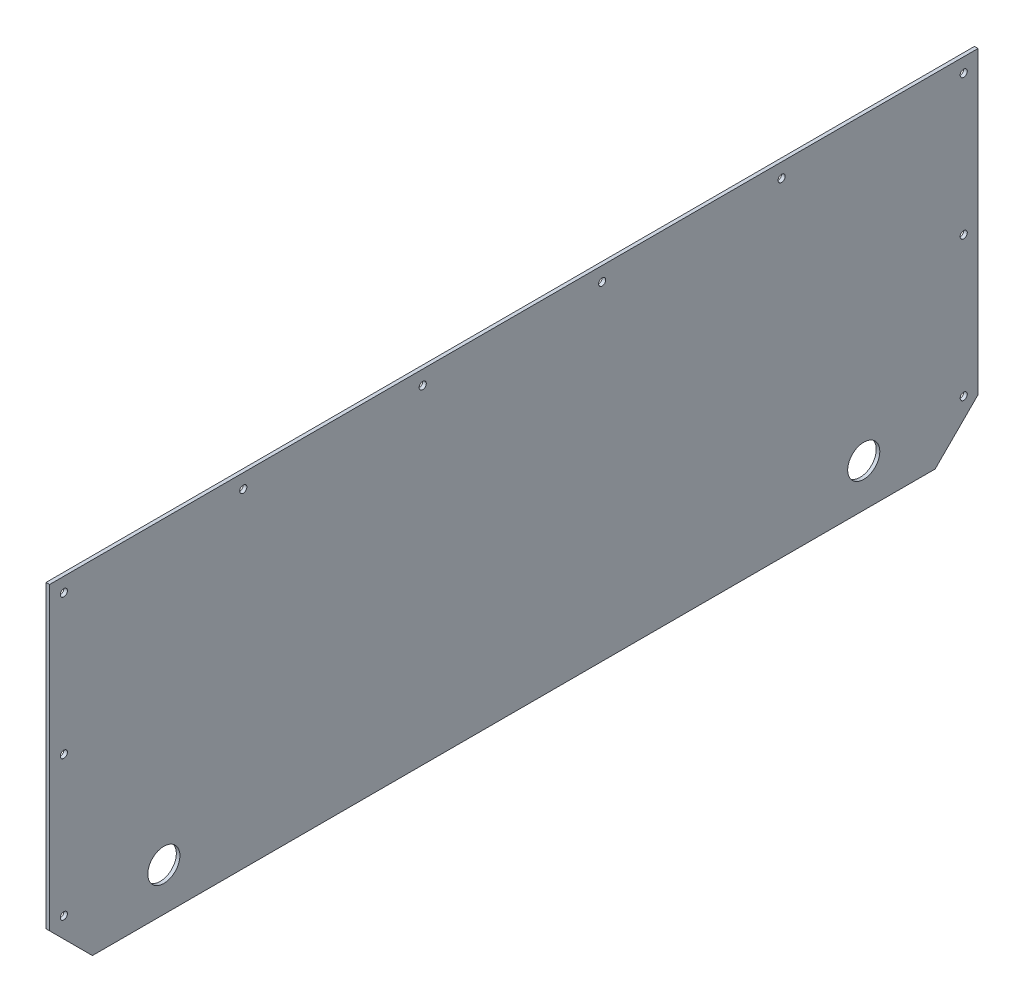
SolidWorks part; units mm, degrees
ref_plane "Front Plane" through (0, 0, 0) normal (0, 0, 1) x (1, 0, 0)
ref_plane "Top Plane" through (0, 0, 0) normal (0, 1, 0) x (1, 0, 0)
ref_plane "Right Plane" through (0, 0, 0) normal (1, 0, 0) x (0, 0, -1)
sketch "Sketch1" plane through (0, 0, 0) normal (0, 0, 1) x (1, 0, 0)
  line L0 (0, 0) -> (0, 304.8)
  dimension "D1" = 304.8
base flange "Base-Flange1" sketch "Sketch1" end condition mid plane depth 825.5 reverse direction no thickness 3.175 reverse thickness direction no bend radius 0.7366
sketch "Sketch6" plane through (3.175, 0, 0) normal (1, 0, 0) x (0, 0, -1)
  line L0 (-311.15, 38.1) -> (311.15, 38.1) construction
  line L1 (-412.75, 0) -> (-412.75, 304.8) construction
  line L2 (-412.75, 0) -> (412.75, 0) construction
  line L3 (-412.75, 38.1) -> (-374.65, 0)
  line L4 (-374.65, 0) -> (-412.75, 0)
  line L5 (-412.75, 0) -> (-412.75, 38.1)
  line L6 (0, 0) -> (0, 304.8) construction
  line L7 (-412.75, 304.8) -> (412.75, 304.8) construction
  line L8 (412.75, 0) -> (412.75, 38.1)
  line L9 (374.65, 0) -> (412.75, 0)
  line L10 (412.75, 38.1) -> (374.65, 0)
  line L11 (-400.05, 25.4) -> (-400.05, 304.8) construction
  line L12 (-412.75, 292.1) -> (412.75, 292.1) construction
  line L13 (412.75, 0) -> (412.75, 304.8) construction
  line L14 (400.05, 304.8) -> (400.05, 25.4) construction
  circle A0 centre (-311.15, 38.1) radius 76.2 construction
  circle A1 centre (311.15, 38.1) radius 76.2 construction
  circle A2 centre (-311.15, 38.1) radius 14.2875
  circle A3 centre (311.15, 38.1) radius 14.2875
  circle A4 centre (-400.05, 292.1) radius 3.175
  circle A5 centre (-400.05, 167.7303) radius 3.175
  circle A6 centre (-400.05, 43.3605) radius 3.175
  circle A7 centre (400.05, 43.3605) radius 3.175
  circle A8 centre (400.05, 292.1) radius 3.175
  circle A9 centre (400.05, 167.7303) radius 3.175
  circle A10 centre (-240.5062, 292.1) radius 3.175
  circle A11 centre (-80.9625, 292.1) radius 3.175
  circle A12 centre (78.5813, 292.1) radius 3.175
  circle A13 centre (238.125, 292.1) radius 3.175
  point P6 (0, 38.1)
  point P10 (-311.15, -38.1)
  dimension "D1" = 152.4
  dimension "D2" = 28.575
  dimension "D9" = 6.35
  dimension "D11" = 12.7
  dimension "D3" = 101.6
  dimension "D4" = 38.1
  dimension "D5" = 38.1
  dimension "D6" = 12.7
  dimension "D7" = 12.7
  dimension "D8" = 12.7
  dimension "D13" = 80.9625
  dimension "D10" = 3
  dimension "D12" = 5
extrude "Cut-Extrude1" cut sketch "Sketch6" against normal through all normal cut yes
sketch "Bend-Lines1" [suppressed] plane through (0, 0, 0) normal (0, 1, 0) x (1, 0, 0)
sketch "Bounding-Box1" [suppressed] plane through (0, 0, 0) normal (0, 1, 0) x (1, 0, 0)
sheet metal parameters "Sheet-Metal1" thickness 3.175 parameters "D1"=0.7366
flat pattern "Flat-Pattern1" [suppressed]
sketch "Bend-Lines2" plane through (0, 0, 0) normal (0, 1, 0) x (1, 0, 0)
sketch3d "Bounding-Box2" [suppressed]
  line L0 (-825.5, 0, 0) -> (0, 0, 0) construction
  line L1 (-825.5, 304.8, 0) -> (0, 304.8, 0) construction
  line L2 (-825.5, 0, 0) -> (-825.5, 304.8, 0) construction
  line L3 (0, 0, 0) -> (0, 304.8, 0) construction
sheet metal parameters "Sheet-Metal2" thickness 3.175 parameters "D1"=0.7366
flat pattern "Flat-Pattern1"
sketch "Bend-Lines2" plane through (0, 0, 0) normal (0, 1, 0) x (1, 0, 0)
sketch3d "Bounding-Box2" [suppressed]
  line L0 (-825.5, 0, 0) -> (0, 0, 0) construction
  line L1 (-825.5, 304.8, 0) -> (0, 304.8, 0) construction
  line L2 (-825.5, 0, 0) -> (-825.5, 304.8, 0) construction
  line L3 (0, 0, 0) -> (0, 304.8, 0) construction
